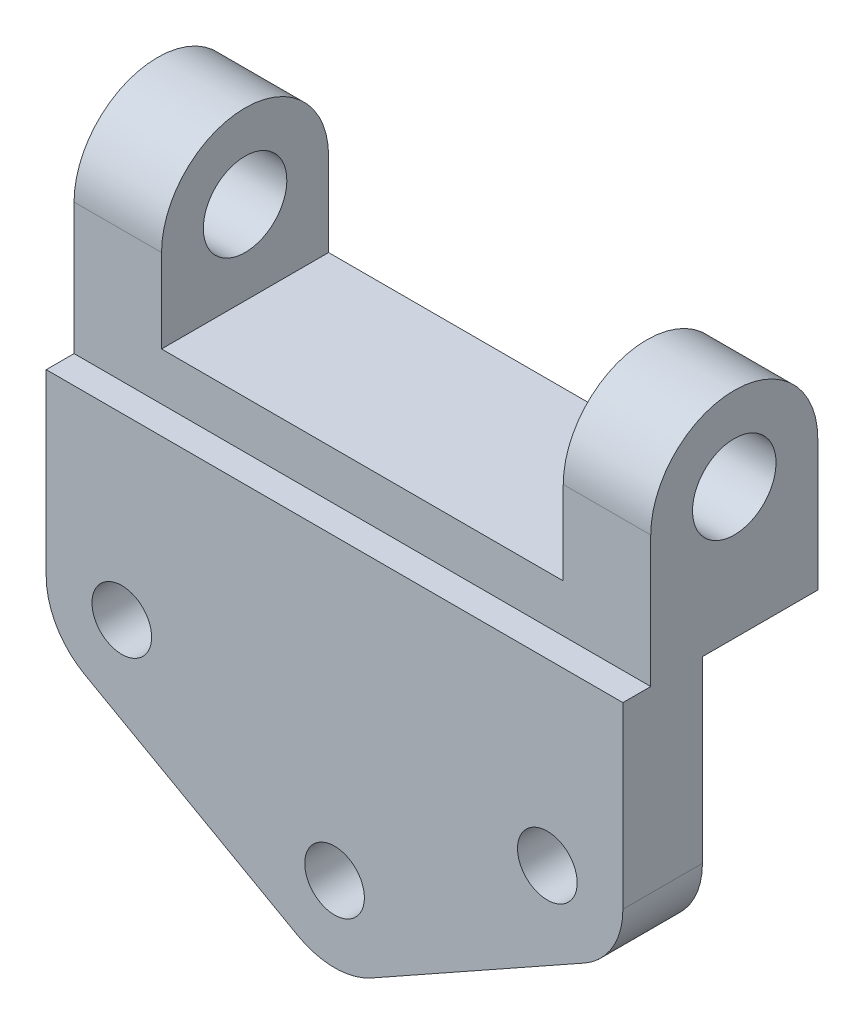
SolidWorks part; units mm, degrees
ref_plane "Front Plane" through (0, 0, 0) normal (0, 0, 1) x (1, 0, 0)
ref_plane "Top Plane" through (0, 0, 0) normal (0, 1, 0) x (1, 0, 0)
ref_plane "Right Plane" through (0, 0, 0) normal (1, 0, 0) x (0, 0, -1)
sketch "Sketch1" plane through (0, 0, 0) normal (0, 0, 1) x (1, 0, 0)
  line L0 (-72.5, 0) -> (-72.5, 54)
  line L1 (-72.5, 54) -> (-50.5, 54)
  line L2 (-50.5, 54) -> (-50.5, 12)
  line L3 (-50.5, 12) -> (50.5, 12)
  line L4 (-72.5, 0) -> (72.5, 0)
  line L5 (-72.5, 0) -> (-72.5, -45)
  line L6 (-62.7929, -61.5723) -> (-9.2929, -91.5723)
  line L7 (0, -99.2383) -> (0, 16.8977) construction
  line L8 (62.7929, -61.5723) -> (9.2929, -91.5723)
  line L9 (72.5, 0) -> (72.5, -45)
  line L10 (50.5, 54) -> (50.5, 12)
  line L11 (72.5, 54) -> (50.5, 54)
  line L12 (72.5, 54) -> (72.5, 0)
  arc A0 (-72.5, -45) -> (-62.7929, -61.5723) centre (-53.5, -45) ccw
  arc A1 (-9.2929, -91.5723) -> (9.2929, -91.5723) centre (0, -75) ccw
  circle A2 centre (0, -75) radius 7.5
  circle A3 centre (-53.5, -45) radius 7.5
  circle A4 centre (53.5, -45) radius 7.5
  arc A5 (72.5, -45) -> (62.7929, -61.5723) centre (53.5, -45) cw
  point P24 (0, 0)
  point P25 (0, 12)
  dimension "D3" = 19
  dimension "D4" = 19
  dimension "D9" = 15
  dimension "D10" = 15
  dimension "D1" = 45
  dimension "D2" = 75
  dimension "D5" = 50.5
  dimension "D6" = 72.5
  dimension "D7" = 12
  dimension "D8" = 54
extrude "Boss-Extrude1" add sketch "Sketch1" along normal blind 20 contours L7 A1 L8 A5 L9 L4 A2 A4 | A1 L7 A2 L4 L5 A0 L6 A3 region at (-32.7597, -38.1718, 0) region at (32.7597, -38.1718, 0)
extrude "Boss-Extrude2" add sketch "Sketch1<3>" along normal blind 42 from offset 29 contours L4 L7 L3 L2 L1 L0 | L7 L4 L12 L11 L10 L3 region at (-71.596, 27, 0) region at (0.904, 6, 0) offset against normal yes
sketch "Sketch1<3>" plane through (0, 0, 0) normal (0, 0, 1) x (1, 0, 0) same geometry as "Sketch1"
sketch "Sketch2" plane through (72.5, 0, 0) normal (1, 0, 0) x (0, 0, -1)
  line L0 (-13, 54) -> (29, 54) construction
  line L1 (29, 54) -> (29, 0) construction
  line L2 (-25.4037, 33) -> (55.57, 33) construction
  circle A0 centre (8, 33) radius 21
  circle A1 centre (8, 33) radius 10.5
  line M5 (29, 0) -> (29, 54)
  line M6 (29, 54) -> (-13, 54)
  line M7 (-13, 54) -> (-13, 0)
  dimension "D1" = 21
  dimension "D2" = 42
extrude "Cut-Extrude1" cut sketch "Sketch2" against normal blind 146 contours A0 M5 M6 | A0 M6 M7 | A1 L2 | A1 region at (72.5, 37.4563, -8) region at (72.5, 49.3093, -24.3093) region at (72.5, 49.3093, 8.3093)
